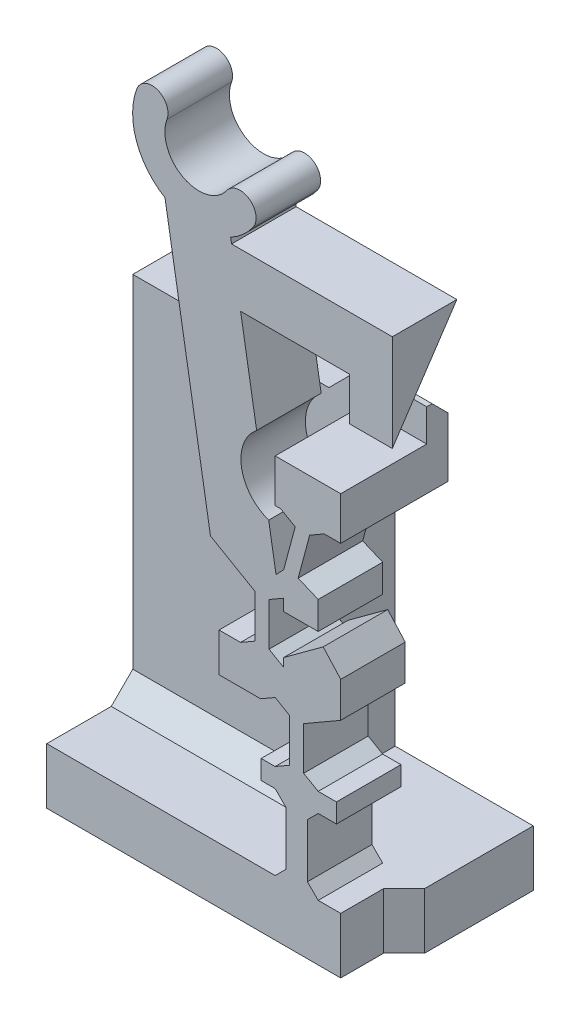
SolidWorks part; units mm, degrees
material "Nylon 6/12"
ref_plane "Front Plane" through (0, 0, 0) normal (0, 0, 1) x (1, 0, 0)
ref_plane "Top Plane" through (0, 0, 0) normal (0, 1, 0) x (1, 0, 0)
ref_plane "Right Plane" through (0, 0, 0) normal (1, 0, 0) x (0, 0, -1)
sketch "Sketch-SkeletonConfigUp" plane through (0, 0, 0) normal (0, 0, 1) x (1, 0, 0)
  line L0 (0, 0) -> (0, -50000) construction
  line L1 (0, 0) -> (4.5811, 6.2164) construction
  line L2 (9.8143, 13.3177) -> (4.5811, 13.945) construction
  line L3 (4.5811, 13.945) -> (2.9713, 10.4094) construction
  line L4 (2.9713, 10.4094) -> (4.5811, 6.2164) construction
  line L5 (4.5811, 13.945) -> (6.2429, 19.1409) construction
  line L6 (2.9713, 10.4094) -> (0.0405, 27.8193) construction
  line L7 (4.5811, 6.2164) -> (9.8143, 13.3177) construction
  line L8 (-587.3593, -797.0242) -> (9.8143, 13.3177) construction
  dimension "D2" = 7.7221
  dimension "D3" = 8.8212
  dimension "D4" = 5.2707
  dimension "D5" = 119.553
  dimension "D6" = 3.8848
  dimension "D7" = 5.4552
  dimension "D8" = 17.6549
  dimension "D9" = 4.4914
  dimension "D10" = 6.745
  dimension "D11" = 145.964
  dimension "D12" = 143.612
sketch "Sketch-SkeletonConfigDown" plane through (0, 0, 0) normal (0, 0, 1) x (1, 0, 0)
  line L0 (0, 0) -> (0, -50000) construction
  line L1 (0, 0) -> (4.5811, 6.2164) construction
  line L2 (9.8143, 13.3177) -> (4.5811, 13.945) construction
  line L3 (4.5811, 13.945) -> (6.1909, 10.4094) construction
  line L4 (6.1909, 10.4094) -> (4.5811, 6.2164) construction
  line L5 (4.5811, 13.945) -> (1.753, 18.6098) construction
  line L6 (6.1909, 10.4094) -> (-8.8652, 19.6294) construction
  line L7 (4.5811, 6.2164) -> (9.8143, 13.3177) construction
  line L8 (-589.9357, -800.5203) -> (9.8143, 13.3177) construction
  dimension "D2" = 7.7221
  dimension "D3" = 8.8212
  dimension "D4" = 5.2707
  dimension "D5" = 119.553
  dimension "D6" = 3.8848
  dimension "D7" = 5.4552
  dimension "D8" = 17.6549
  dimension "D9" = 4.4914
  dimension "D10" = 6.745
  dimension "D11" = 145.964
  dimension "D1" = 143.612
ref_plane "Plane-Cam Base" through (9.128, 0, 0) normal (1, 0, 0) x (0, 0, -1)
ref_plane "Plane-Down-to-Up Derailleur Clearance" through (6.628, 0, 0) normal (1, 0, 0) x (0, 0, -1)
ref_plane "Plane-Cam Cavity Roof" through (5.128, 0, 0) normal (1, 0, 0) x (0, 0, -1)
sketch "Sketch-SwitchBossUp" plane through (0, 0, 0) normal (0, 0, 1) x (1, 0, 0)
  line L0 (3.5811, 11.4759) -> (3.5811, 12.945) construction
  line L5 (5.5811, 12.5552) -> (5.5811, 11.263)
  line L7 (1.5115, 25.1048) -> (1.5536, 24.8548)
  line L8 (-0.4607, 24.7728) -> (1.6966, 11.9577) construction
  line L9 (2.9713, 10.4094) -> (0.0405, 27.8193) construction
  line L11 (0.1364, 21.2256) -> (2.1086, 21.5576) construction
  line L15 (6.628, -23.7286) -> (6.628, 23.7286) construction
  line L16 (2.9713, 10.4094) -> (4.5811, 6.2164) construction
  line L17 (3.5811, 12.945) -> (3.5811, 14.945) construction
  line L18 (5.5811, 12.945) -> (5.5811, 14.945) construction
  line L19 (4.2561, 13.945) -> (4.9061, 13.945) construction
  line L20 (3.5811, 14.945) -> (5.5811, 14.945) construction
  line L21 (3.5811, 12.945) -> (5.5811, 12.945) construction
  line L22 (4.5811, 12.945) -> (4.5811, 14.945) construction
  line L23 (4.5811, 6.2164) -> (8.5405, 7.1023) construction
  line L24 (1.9713, 9.4094) -> (1.9713, 11.4094) construction
  line L25 (3.9713, 9.4094) -> (3.9713, 11.4094) construction
  line L26 (3.9713, 9.4094) -> (1.9713, 9.4094) construction
  line L27 (1.9713, 11.4094) -> (3.9713, 11.4094) construction
  line L28 (3.5811, 7.2164) -> (5.5811, 7.2164) construction
  line L29 (3.5811, 7.2164) -> (3.5811, 5.2164) construction
  line L30 (5.5811, 7.2164) -> (5.5811, 5.2164) construction
  line L31 (3.5811, 5.2164) -> (5.5811, 5.2164) construction
  line L32 (4.9061, 6.2164) -> (4.2561, 6.2164) construction
  line L40 (3.2963, 10.4094) -> (2.6463, 10.4094) construction
  line L66 (0.0405, 27.8193) -> (0.0405, 50027.8193) construction
  line L75 (4.5811, 3.937) -> (4.5811, 0.437) construction
  line L76 (5.5811, 11.263) -> (5.5811, 12.5552) construction
  line L77 (5.5811, 7.6061) -> (6.628, 8.2105)
  line L80 (5.8152, 10.763) -> (6.628, 9.8603)
  line L81 (9.128, 1033.2419) -> (9.128, 20.0586) construction
  line L85 (6.9307, 9.5241) -> (8.5405, 7.7363) construction
  line L88 (5.7256, 17.3347) -> (6.628, 17.3347)
  line L92 (3.7762, 8.3129) -> (6.9307, 9.5241) construction
  line L98 (1.9713, 9.0197) -> (0.9713, 9.0197)
  line L99 (0.9713, 9.0197) -> (0.9713, 7.2164)
  line L100 (0.9713, 7.2164) -> (2.9061, 7.2164)
  line L101 (4.5811, 6.2164) -> (6.9307, 9.5241) construction
  line L103 (0.0405, 27.8193) -> (1.9448, 26.4638) construction
  line L104 (6.9307, 9.5241) -> (8.5405, 7.7363) construction
  line L107 (1.9713, 9.4094) -> (1.9713, 9.0197) construction
  line L109 (0.0405, 27.8193) -> (-2.1498, 28.6358) construction
  line L111 (6.628, 9.8603) -> (6.628, 8.2105)
  line L112 (6.628, 9.8603) -> (6.9307, 9.5241) construction
  line L113 (2.9306, 4.8267) -> (2.9306, 3.937)
  line L114 (7.3693, 7.7363) -> (7.3563, 7.7363) construction
  line L121 (5.0811, -2.0859) -> (5.0811, 0.437) construction
  line L122 (9.028, 22.3548) -> (9.028, 20.3548)
  line L127 (5.5811, 15.3347) -> (5.5811, 14.945) construction
  line L133 (2.9713, 10.4094) -> (6.1909, 10.4094) construction
  line L134 (4.5811, 10.4094) -> (4.5811, 13.945) construction
  line L135 (4.5811, 10.4094) -> (4.5811, 6.2164) construction
  line L137 (3.9713, 9.4094) -> (5.5811, 7.2164) construction
  line L139 (5.8152, 10.763) -> (3.9713, 9.4094)
  line L142 (3.0345, 0.437) -> (3.0345, -2.1653)
  line L143 (9.128, 20.0586) -> (9.128, 18.3333) construction
  line L145 (9.128, 16.6071) -> (9.128, -49992.4167) construction
  line L147 (5.5811, 11.263) -> (5.5811, 12.5552) construction
  line L150 (3.0345, -2.1653) -> (6.628, -2.1653)
  line L151 (4.0811, 3.937) -> (5.0811, 3.937) construction
  line L152 (4.5126, 14.945) -> (3.9767, 12.945)
  line L153 (5.1855, 14.945) -> (4.6496, 12.945)
  line L157 (3.5811, 17.3347) -> (3.5811, 15.3347)
  line L158 (5.8605, 15.3347) -> (6.628, 15.3347)
  line L162 (3.2963, 11.4094) -> (3.2963, 9.4094)
  line L164 (2.6463, 11.4094) -> (2.6463, 9.4094)
  line L169 (4.2561, 7.2164) -> (4.2561, 5.2164)
  line L170 (4.9061, 5.2164) -> (4.9061, 7.2164)
  line L175 (4.2561, 7.2164) -> (3.5811, 7.6061)
  line L176 (4.9061, 7.2164) -> (5.5811, 7.6061)
  line L177 (5.5811, 7.2164) -> (5.5811, 7.6061) construction
  line L179 (4.2561, 5.2164) -> (3.5811, 4.8267)
  line L180 (3.5811, 5.2164) -> (3.5811, 4.8267) construction
  line L181 (3.5811, 4.8267) -> (2.9306, 4.8267)
  line L183 (4.9061, 5.2164) -> (5.5811, 4.8267)
  line L184 (5.5811, 5.2164) -> (5.5811, 4.8267) construction
  line L186 (9.128, -23.7286) -> (9.128, 23.7286) construction
  line L187 (2.6463, 9.4094) -> (1.9713, 9.0197)
  line L188 (3.2963, 9.4094) -> (3.9713, 9.0197)
  line L189 (3.2963, 11.4094) -> (3.9713, 11.7991)
  line L190 (2.6463, 11.4094) -> (1.6966, 11.9577)
  line L191 (3.9713, 11.4094) -> (3.9713, 11.7991) construction
  line L192 (3.9713, 11.7991) -> (3.9713, 11.263)
  line L193 (4.6496, 12.945) -> (5.5811, 12.5552)
  line L194 (3.9767, 12.945) -> (3.6203, 12.5779)
  line L195 (3.9713, 11.263) -> (5.5811, 11.263)
  line L196 (3.9713, 9.4094) -> (3.9713, 9.0197)
  line L197 (3.5811, 7.2164) -> (3.5811, 7.6061) construction
  line L199 (3.5811, 7.6061) -> (2.9061, 7.2164)
  line L201 (2.9306, 4.3267) -> (2.9306, 3.937) construction
  line L202 (2.9306, 3.937) -> (4.0811, 3.937) construction
  line L207 (9.128, 18.3333) -> (9.128, 16.6071) construction
  line L208 (6.628, -2.1653) -> (6.628, 0.437)
  line L209 (9.128, 20.0586) -> (9.128, 16.6071) construction
  line L211 (5.0811, 0.937) -> (5.0811, 3.437)
  line L212 (4.0811, 0.937) -> (4.0811, 3.437)
  line L214 (4.5126, 14.945) -> (3.8375, 15.3347)
  line L215 (3.8375, 15.3347) -> (3.5811, 15.3347)
  line L216 (5.1855, 14.945) -> (5.8605, 15.3347)
  line L217 (5.5811, 12.945) -> (5.5811, 12.5552) construction
  line L218 (5.1855, 14.945) -> (5.1855, 15.3347) construction
  line L219 (5.8605, 15.3347) -> (3.8375, 15.3347) construction
  line L221 (9.028, 22.3548) -> (9.028, 24.8548)
  line L224 (3.5811, 17.3347) -> (5.7256, 17.3347)
  line L232 (6.628, 15.3347) -> (6.628, 17.3347)
  line L236 (1.5536, 24.8548) -> (9.028, 24.8548)
  line L240 (5.5811, 3.937) -> (6.4306, 3.937)
  line L248 (7.028, 22.3548) -> (1.9744, 22.3548)
  line L249 (1.9744, 22.3548) -> (2.7198, 17.9273)
  line L250 (9.028, 20.3548) -> (7.028, 20.3548)
  line L251 (7.028, 20.3548) -> (7.028, 22.3548)
  line L252 (3.2801, 14.5986) -> (3.6203, 12.5779)
  line L253 (4.2672, 14.0291) -> (4.895, 13.8608) construction
  line L254 (5.0811, 0.437) -> (4.0811, 0.437) construction
  line L255 (4.0811, 0.437) -> (3.0345, 0.437) construction
  line L256 (4.5811, 6.2164) -> (4.5811, 3.937) construction
  line L257 (3.5811, 0.437) -> (3.0345, 0.437)
  line L259 (5.5811, 0.437) -> (6.628, 0.437)
  line L261 (1.6966, 11.9577) -> (0.5733, 12.6062)
  line L262 (0.5733, 12.6062) -> (-1.5413, 25.1678)
  line L263 (4.0811, 3.437) -> (3.5811, 3.937)
  line L266 (5.0811, 3.437) -> (5.5811, 3.937)
  line L270 (3.5811, 0.437) -> (4.0811, 0.937)
  line L275 (5.0811, 0.937) -> (5.5811, 0.437)
  line L277 (3.5811, 3.937) -> (2.9306, 3.937)
  line L367 (5.5811, 4.8267) -> (6.4306, 4.8267)
  line L368 (6.4306, 4.8267) -> (6.4306, 3.937)
  arc A0 (1.5115, 25.1048) -> (2.5558, 26.0289) centre (0.0405, 27.8193) ccw
  arc A1 (-1.5413, 25.1678) -> (-2.8525, 28.8978) centre (0.0405, 27.8193) cw
  arc A2 (-2.8525, 28.8978) -> (-1.447, 28.3738) centre (-2.1498, 28.6358) cw
  arc A3 (2.5558, 26.0289) -> (1.3338, 26.8987) centre (1.9448, 26.4638) ccw
  arc A4 (-1.447, 28.3738) -> (1.3338, 26.8987) centre (0.0405, 27.8193) ccw
  arc A5 (3.5811, 12.945) -> (3.5811, 14.945) centre (3.1778, 13.945) ccw construction
  arc A6 (5.5811, 12.945) -> (5.5811, 14.945) centre (5.9843, 13.945) cw construction
  arc A7 (2.528, 9.9183) -> (1.9713, 11.4094) centre (1.568, 10.4094) ccw construction
  arc A8 (3.9713, 11.4094) -> (3.9713, 9.4094) centre (4.3745, 10.4094) ccw construction
  arc A9 (3.5811, 7.2164) -> (3.5811, 5.2164) centre (3.1779, 6.2164) cw construction
  arc A10 (5.5811, 7.2164) -> (5.5811, 5.2164) centre (5.9844, 6.2164) ccw construction
  circle A28 centre (0.0405, 27.8193) radius 2.3375 construction
  arc A29 (1.9713, 9.4094) -> (2.528, 9.9183) centre (1.568, 10.4094) ccw construction
  arc A30 (3.2801, 14.5986) -> (2.7198, 17.9273) centre (3.9114, 16.4164) cw
  arc A31 (-0.4607, 24.7728) -> (-1.5413, 25.1678) centre (0.0405, 27.8193) cw construction
  point P53 (4.5811, 13.945)
  point P63 (2.9713, 10.4094)
  point P83 (5.6082, 3.9455)
  point P93 (1.1225, 21.3916)
  point P107 (6.4175, 3.937)
  dimension "D23" = 1.5875
  dimension "D24" = 0.75
  dimension "D2" = 2
  dimension "D5" = 2
  dimension "D8" = 42
  dimension "D16" = 42
  dimension "D27" = 120
  dimension "D28" = 120
  dimension "D29" = 120
  dimension "D30" = 120
  dimension "D31" = 120
  dimension "D32" = 120
  dimension "D33" = 120
  dimension "D34" = 120
  dimension "D21" = 2
  dimension "D38" = 2
  dimension "D39" = 0.5
  dimension "D40" = 60
  dimension "D41" = 1
  dimension "D42" = 45
  dimension "D43" = 120
  dimension "D25" = 15
  dimension "D26" = 120
  dimension "D35" = 120
  dimension "D83" = 3.5
  dimension "D14" = 2.5
  dimension "D15" = 0.25
  dimension "D7" = 2
  dimension "D9" = 2
  dimension "D6" = 0.65
  dimension "D12" = 1
  dimension "D18" = 3.5
  dimension "D19" = 0.65
  dimension "D20" = 1
  dimension "D10" = 19.5
extrude "Boss-Switch Body" add sketch "Sketch-SwitchBossUp" along normal blind 3
sketch "Sketch1" plane through (0, 0, 0) normal (0, 0, -1) x (-1, 0, 0)
  line L1 (-7.5811, -2.1653) -> (0.4122, -2.1653)
  line L2 (-7.5811, -2.1653) -> (-7.5811, 0.437)
  line L4 (0.4122, -2.1653) -> (0.4122, 0.437)
  line L5 (-3.5811, 18.8347) -> (-7.5811, 18.8347)
  line L10 (-7.5811, 18.8347) -> (-7.5811, 15.3347)
  line L11 (-3.5811, 0.437) -> (-5.0811, 0.437)
  line L12 (-7.5811, 15.3347) -> (-3.5811, 15.3347)
  line L13 (-3.5811, 0.437) -> (-3.0345, 0.437)
  line L14 (-3.5811, 15.3347) -> (-3.5811, 18.8347)
  line L20 (-5.0811, 3.437) -> (-5.0811, 0.937) construction
  line L22 (-3.0345, -2.1653) -> (-6.628, -2.1653) construction
  line L23 (-3.0345, 0.437) -> (0.4122, 0.437)
  line L24 (-5.0811, 0.437) -> (-6.628, 0.437)
  line L25 (-6.628, 0.437) -> (-7.5811, 0.437)
  point P5 (-3.5811, 0.437)
  dimension "D1" = 3.5
extrude "Boss-Flange Width" add sketch "Sketch1" along normal blind 5
ref_plane "Plane-Sta2Sit Groove" through (0.0405, 0, 0) normal (1, 0, 0) x (0, 0, -1)
ref_plane "Plane-Cam Outer Surface" through (-12.0395, 0, 0) normal (1, 0, 0) x (0, 0, -1)
ref_plane "Plane-FlangeTop" through (-7.0395, 0, 0) normal (1, 0, 0) x (0, 0, -1)
sketch "Sketch2" plane through (-7.0395, 0, 0) normal (1, 0, 0) x (0, 0, -1)
  line L0 (5, 15.3347) -> (-3, 15.3347) construction
  line L1 (5, 17.3347) -> (1, 17.3347)
  line L2 (5, 17.3347) -> (5, 15.3347)
  line L3 (5, 15.3347) -> (1, 15.3347)
  line L4 (1, 17.3347) -> (1, 15.3347)
  line L5 (-3, -2.1653) -> (-3, 0.437) construction
  line L11 (5, 0.437) -> (-3, 0.437)
  line L12 (5, 0.437) -> (5, -2.1653)
  line L13 (5, -2.1653) -> (-3, -2.1653)
  line L14 (-3, 0.437) -> (-3, -2.1653)
  line L15 (0, 10.4094) -> (0, 27.8193) construction
  line L17 (5, 0.437) -> (5, -2.1653) construction
  line L18 (-3, 0.437) -> (0, 0.437) construction
  dimension "D1" = 1
  dimension "D2" = 2
extrude "Boss-Flange Height" add sketch "Sketch2" along normal up to surface (11.6675 mm away)
sketch "Sketch10" plane through (0, 15.3347, 0) normal (0, 1, 0) x (1, 0, 0)
  line L0 (9.128, -23.7286) -> (9.128, 23.7286) construction
  line L1 (7.5811, 5) -> (5.128, 5)
  line L2 (7.5811, 5) -> (7.5811, 2)
  line L3 (7.5811, 2) -> (5.128, 2)
  line L5 (4.628, 7) -> (4.628, 1) construction
  line L6 (3.5811, 1) -> (-7.0395, 1) construction
  line L8 (5.128, 5) -> (5.128, 2)
  dimension "D1" = 1
  dimension "D2" = 0.5
  dimension "D3" = 4.5
extrude "Cut-Up-To-Down Derailleur Clearance" cut sketch "Sketch10" along normal up to next
sketch "Sketch17" plane through (0, 15.3347, 0) normal (0, -1, 0) x (1, 0, 0)
  line L0 (5.128, -5) -> (-7.0395, -5)
  line L1 (5.128, -5) -> (-7.0395, -5) construction
  line L2 (-7.0395, -5) -> (-7.0395, -1)
  line L3 (-7.0395, -1) -> (5.128, -1)
  line L4 (5.128, -1) -> (5.128, -5)
  line L5 (-7.0395, -1) -> (-7.0395, -5) construction
extrude "Boss-Flange Support" add sketch "Sketch17" along normal up to surface (14.8977 mm away) up to face at (3.2664, 0.437, 0.2)
sketch "Sketch-HolePositions" plane through (0, -2.1653, 0) normal (0, -1, 0) x (1, 0, 0)
  line L0 (-7.0395, -3) -> (7.5811, -3) construction
  line L1 (7.5811, -5) -> (-7.0395, -5) construction
  line L2 (7.5811, -5) -> (7.5811, 0) construction
  line L4 (-7.0395, -22.2167) -> (-7.0395, 22.2167) construction
  point P6 (-5.0395, -3)
  point P7 (-0.5395, -3)
  dimension "D1" = 2
  dimension "D2" = 4.5
  dimension "D3" = 2
sketch "Sketch6" plane through (0, -2.1653, 0) normal (0, -1, 0) x (-1, 0, 0)
  point P0 (5.0395, 3)
  point P3 (0.5395, 3)
hole_wizard "Tap Drill for M2x0.4 Tap1" positions "Sketch6" profile "Sketch5" hole size "M2x0.4" standard "ANSI Metric" end condition through all
sketch "Sketch5" plane through (-5.0395, -2.1653, -3) normal (1, 0, 0) x (0, 0, -1)
  line L0 (0, 0) -> (0, 31.5511)
  line L1 (0, 31.5511) -> (0.8, 31.5511)
  line L2 (0.8, 31.5511) -> (0.8, 0)
  line L5 (0.8, 0) -> (0, 0)
  line L11 (0, -6.35) -> (0, 107.95) construction
  dimension "Thru Hole Dia." = 1.6
  dimension "Thru Hole Depth" = 31.5511
sketch "Sketch9" plane through (0, -2.1653, 0) normal (0, -1, 0) x (1, 0, 0)
  point P0 (-5.0395, -3)
  point P3 (-0.5395, -3)
hole_wizard "M2 Clearance Hole2" positions "Sketch9" profile "Sketch8" hole size "M2" standard "ANSI Metric"
sketch "Sketch8" plane through (-5.0395, -2.1653, -3) normal (1, 0, 0) x (0, 0, -1)
  line L0 (0, 0) -> (0, 15.721)
  line L1 (0, 15.721) -> (1.2, 15)
  line L2 (1.2, 15) -> (1.2, 0)
  line L5 (1.2, 0) -> (0, 0)
  line L10 (0, 15.721) -> (-1.2, 15) construction
  line L11 (0, -6.35) -> (0, 107.95) construction
  dimension "Hole Dia." = 2.4
  dimension "Hole Depth" = 15
  dimension "Drill Angle" = 118
sketch "Sketch-Measurements for Derailleur Ramps" [suppressed] plane through (0, 0, 0) normal (0, 0, 1) x (1, 0, 0)
  line L0 (3.184, 15.1695) -> (2.4687, 19.4188)
  line L1 (2.8264, 17.2941) -> (1.8402, 17.1281)
  line L2 (2.9713, 10.4094) -> (0.0405, 27.8193) construction
  line L3 (1.8402, 17.1281) -> (-1.3081, 15.0016)
  line L4 (6.1909, 10.4094) -> (-8.8652, 19.6294) construction
  line L5 (1.8402, 17.1281) -> (2.6012, 12.6077)
  line L6 (2.6012, 12.6077) -> (-1.3081, 15.0016)
  line L7 (0.2661, 16.0649) -> (0.2661, 17.1281)
  line L8 (0.2661, 17.1281) -> (1.8402, 17.1281)
  line L9 (6.1909, 10.4094) -> (2.9713, 10.4094)
  line L10 (5.386, 8.3129) -> (3.7762, 8.3129)
  line L11 (2.6116, 18.5698) -> (1.5115, 25.1048) construction
  line L12 (6.1909, 10.4094) -> (4.5811, 6.2164) construction
  line L13 (4.5811, 8.3129) -> (4.5811, 8.7912)
  line L14 (4.5811, 6.2164) -> (5.386, 8.3129)
  line L15 (2.9713, 10.4094) -> (4.5811, 6.2164) construction
  line L16 (3.7762, 8.3129) -> (4.5811, 6.2164)
  line L17 (5.386, 8.3129) -> (5.386, 8.7912)
  dimension "D1" = 1.5742
  dimension "D2" = 0.8049
ref_plane "Plane1" through (0, 7.1023, 0) normal (0, 1, 0) x (1, 0, 0)
ref_plane "Plane-Cantilever Cut" [suppressed] through (7.0848, 8.5204, -1.9058) normal (-0.6301, -0.7578, 0.1695) x (-0.7765, 0.6151, -0.1368)
sketch "Sketch14" [suppressed] plane through (7.0848, 8.5204, -1.9058) normal (-0.6301, -0.7578, 0.1695) x (-0.7765, 0.6151, -0.1368)
  line L0 (2.3023, -1.6911) -> (-0.3551, -1.6911)
  line L2 (2.3023, -4.3362) -> (2.3023, -1.6911)
  line L3 (-0.3551, -1.6911) -> (-0.3551, -4.4608)
  line L5 (-0.3551, -4.4608) -> (1.0087, -5.0843)
  line L6 (1.0087, -5.0843) -> (2.3023, -4.3362)
extrude "Cut-Down-to-Up Cantilever Slope" [suppressed] cut sketch "Sketch14" against normal up to next
ref_plane "Plane-Symmetry Plane" through (0, 0, 1.5) normal (0, 0, 1) x (1, 0, 0)
sketch "Sketch-Cable Center Point" plane through (0, 0, 1.5) normal (0, 0, 1) x (1, 0, 0)
  line L0 (0.0405, 27.8193) -> (0.1722, 27.0366)
  line L1 (2.9713, 10.4094) -> (0.0405, 27.8193) construction
  point P0 (0.0405, 27.8193)
  dimension "D1" = 0.7937
chamfer "Chamfer-Flange Support" distance 1.5 angle 45 1 edges at (3.5811, 17.3347, -3)
chamfer "Chamfer-Flange Support 2" distance 1.5 angle 45 2 edges at (5.128, 17.0847, -2) (5.128, 15.3347, -1.5)
chamfer "Chamfer7" [suppressed] distance 1 angle 45
sketch "Sketch23" plane through (0, 0, -1) normal (0, 0, 1) x (1, 0, 0)
  line L0 (5.128, 0.437) -> (1.1605, 0.437)
  line L2 (1.1605, 0.437) -> (1.1605, 13.8347)
  line L3 (1.1605, 13.8347) -> (5.128, 13.8347)
  line L4 (5.128, 13.8347) -> (5.128, 0.437)
  line L5 (0.6605, -2.1653) -> (0.6605, 12.8347) construction
  line L6 (3.5811, 0.437) -> (-7.0395, 0.437) construction
  point P3 (1.1605, 0.437)
  point P11 (5.128, 1.437)
  point P12 (5.128, 0.437)
  dimension "D1" = 0.5
extrude "Cut-Gap for Printing" cut sketch "Sketch23" against normal through all
chamfer "Chamfer-Flange Support 3" distance 1 angle 45 1 edges at (-2.9395, 0.437, -1)
sketch "Sketch25" plane through (0, 0, 0) normal (0, 0, 1) x (1, 0, 0)
  line L0 (6.628, 15.3347) -> (7.5811, 15.3347)
  line L1 (7.5811, 15.3347) -> (7.5811, 18.8347)
  line L2 (7.5811, 18.8347) -> (6.628, 18.8347)
  line L3 (6.628, -23.7286) -> (6.628, 23.7286) construction
  line L4 (7.5811, 18.8347) -> (3.5811, 18.8347) construction
  line L5 (6.628, 18.8347) -> (6.628, 15.3347)
  line L6 (7.5811, 18.8347) -> (7.5811, 15.3347) construction
extrude "Cut-Derailleur Clearance" cut sketch "Sketch25" against normal through all
chamfer "Chamfer8" distance 1 angle 45 1 edges at (6.628, -0.8641, 0)
ref_plane "Plane2" through (-3.0866, 5.589, 8.3835) normal (0.2929, -0.5304, -0.7956) x (-0.9561, -0.1625, -0.2437)
sketch "Sketch26" plane through (-3.0866, 5.589, 8.3835) normal (0.2929, -0.5304, -0.7956) x (-0.9561, -0.1625, -0.2437)
  line L0 (-7.553, 20.6804) -> (-7.553, 14.9094)
  line L1 (-12.6703, 20.6804) -> (-5.5238, 20.6804) construction
  line L3 (-7.553, 14.9094) -> (-20.0302, 14.9094)
  line L4 (-20.0302, 14.9094) -> (-20.0302, 20.6804)
  line L5 (-20.0302, 20.6804) -> (-7.553, 20.6804)
extrude "Cut-Up-to-Down Cantilever Slope" cut sketch "Sketch26" along normal up to next
sketch "Sketch27" plane through (5.128, 0, 0) normal (1, 0, 0) x (0, 0, -1)
  line L0 (3.5, 18.8347) -> (3.5, 13.8347) construction
  line L1 (2.5, 18.8347) -> (5, 18.8347)
  line L2 (2.5, 18.8347) -> (2.5, 13.8347)
  line L3 (2.5, 13.8347) -> (5, 13.8347)
  line L4 (5, 18.8347) -> (5, 13.8347)
  dimension "D1" = 1
extrude "Cut-Wide Derailleur Clearance" cut sketch "Sketch27" against normal blind 4 and the other way through all
chamfer "Chamfer9" distance 1.25 angle 45 1 edges at (4.8545, 18.8347, -2.5)
sketch "Sketch28" plane through (0, 0, -1) normal (0, 0, 1) x (1, 0, 0)
  line L0 (3.5811, 18.8347) -> (6.628, 18.8347)
  line L1 (6.628, 18.8347) -> (6.628, 17.3347)
  line L2 (6.628, 17.3347) -> (3.5811, 17.3347)
  line L3 (3.5811, 17.3347) -> (3.5811, 18.8347)
extrude "Cut-Extrude1" cut sketch "Sketch28" along normal up to surface (1 mm away) up to face at (5.1045, 18.0847, 0)
equation "\"axle-diameter\"=2"
equation "\"switch-thickness\"=12"
equation "\"base-width\"=4.0"
equation "\"axle-bushing-radius\"=3"
equation "\"clearance\"= 0.25"
equation "\"arm-width\"=1.5"
equation "\"min-diameter\"=70"
equation "\"alpha\"=143.6120"
equation "\"gamma\"=119.5526"
equation "\"delta\"=145.9637"
equation "\"epsilon\"=6.7452"
equation "\"l_AB\"=8.8212"
equation "\"l_AC\"=4.4914"
equation "\"l_BD\"=5.2707"
equation "\"l_CD\"=3.8848"
equation "\"l_CE\"=17.6549"
equation "\"l_DF\"=5.4552"
equation "\"l_OA\"=7.7221"
equation "\"D2@Sketch-SkeletonConfigUp\" = \"l_OA\""
equation "\"D3@Sketch-SkeletonConfigUp\" = \"l_AB\""
equation "\"D4@Sketch-SkeletonConfigUp\" = \"l_BD\""
equation "\"D5@Sketch-SkeletonConfigUp\" = \"gamma\""
equation "\"D6@Sketch-SkeletonConfigUp\" = \"l_CD\""
equation "\"D7@Sketch-SkeletonConfigUp\" = \"l_DF\""
equation "\"D8@Sketch-SkeletonConfigUp\" = \"l_CE\""
equation "\"D9@Sketch-SkeletonConfigUp\" = \"l_AC\""
equation "\"D_groove\"=3.175"
equation "\"D7@Sketch-SkeletonConfigDown\" = \"l_DF\""
equation "\"D6@Sketch-SkeletonConfigDown\" = \"l_CD\""
equation "\"D2@Sketch-SkeletonConfigDown\" = \"l_OA\""
equation "\"D3@Sketch-SkeletonConfigDown\" = \"l_AB\""
equation "\"D9@Sketch-SkeletonConfigDown\" = \"l_AC\""
equation "\"D8@Sketch-SkeletonConfigDown\" = \"l_CE\""
equation "\"D5@Sketch-SkeletonConfigDown\" = \"gamma\""
equation "\"D4@Sketch-SkeletonConfigDown\" = \"l_BD\""
equation "\"D1@Sketch-SkeletonConfigDown\" = \"alpha\""
equation "\"hinge_length\"=1.5"
equation "\"hinge_depth\"=0.25"
equation "\"D10@Sketch-SkeletonConfigUp\"=\"epsilon\""
equation "\"D11@Sketch-SkeletonConfigUp\"=\"delta\""
equation "\"D12@Sketch-SkeletonConfigUp\"=\"alpha\""
equation "\"D11@Sketch-SkeletonConfigDown\"=\"delta\""
equation "\"D10@Sketch-SkeletonConfigDown\"=\"epsilon\""
equation "\"EE_dx\"=8.9056"
equation "\"EE_dy\"=8.1898"
equation "\"r_groove\"=\"D_groove\"/2"
equation "\"t_wall\"=25.4/16"
equation "\"width_lower\"=\"D_groove\"+\"t_wall\""
equation "\"cable_to_bottom\"=30.6257"
equation "\"switch_EE-up_base_dy\"=24"
equation "\"switch_EE-down_base_dy\"=16"
equation "\"D_axle\"=25.4/8"
equation "\"D_up_to_down\"=16"
equation "\"D_down_to_up\"=25"
equation "\"t_cam_base\"=7.5"
equation "\"D23@Sketch-SwitchBossUp\"=\"D_groove\"/2"
equation "\"D1@Sketch-Cable Center Point\"=\"D_groove\"/4"
